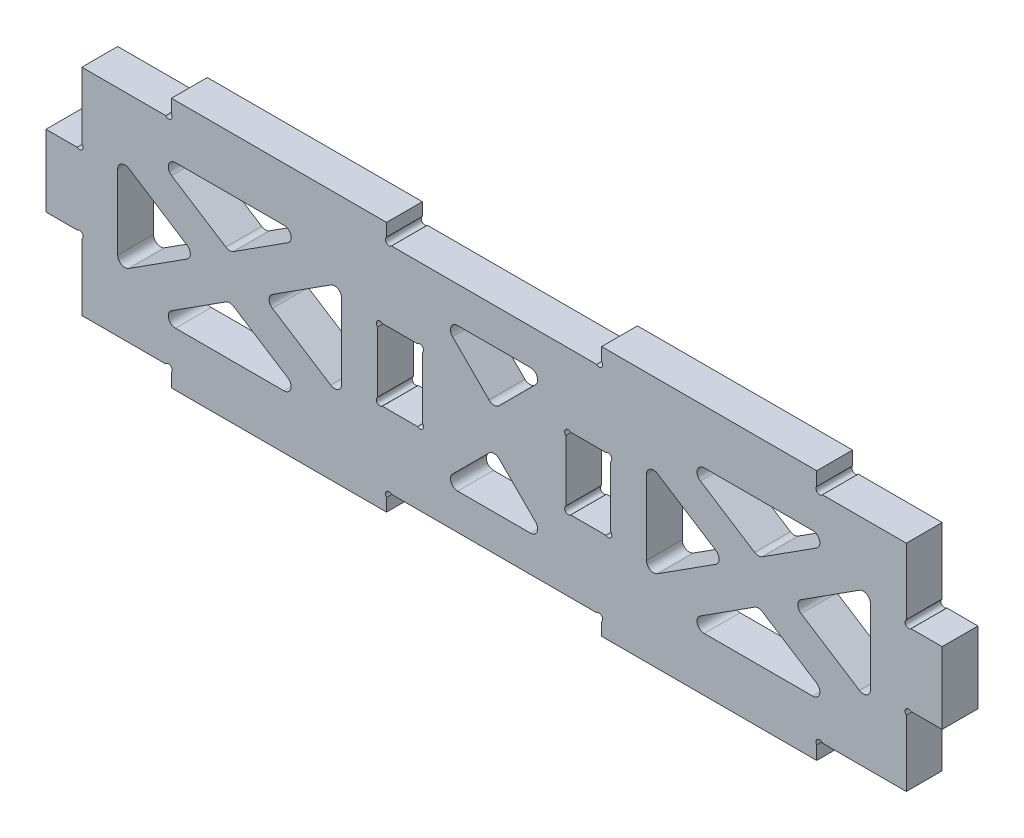
SolidWorks part; units mm, degrees
material "7050-T73510"
ref_plane "Front Plane" through (0, 0, 0) normal (0, 0, 1) x (1, 0, 0)
ref_plane "Top Plane" through (0, 0, 0) normal (0, 1, 0) x (1, 0, 0)
ref_plane "Right Plane" through (0, 0, 0) normal (1, 0, 0) x (0, 0, -1)
sketch "Sketch1" plane through (0, 0, 0) normal (0, 0, 1) x (1, 0, 0)
  line L1 (-158.75, -38.1) -> (158.75, -38.1)
  line L2 (-158.75, -38.1) -> (-158.75, 38.1)
  line L3 (-158.75, 38.1) -> (158.75, 38.1)
  line L4 (158.75, -38.1) -> (158.75, 38.1)
  line L5 (-158.75, -38.1) -> (158.75, 38.1) construction
  line L6 (-158.75, 38.1) -> (158.75, -38.1) construction
  point P0 (0, 0)
  dimension "D1" = 317.5
  dimension "D2" = 76.2
extrude "Boss-Extrude1" add sketch "Sketch1" along normal blind 12.7 contours L1 L3 region at (0, 0, 0)
sketch "Sketch2" plane through (0, 0, 12.7) normal (0, 0, 1) x (1, 0, 0)
  line L0 (-158.75, -38.1) -> (158.75, -38.1) construction
  line L1 (-38.1, -38.1) -> (-114.3, -38.1)
  line L2 (-38.1, -38.1) -> (-38.1, -44.45)
  line L3 (-38.1, -44.45) -> (-114.3, -44.45)
  line L4 (-114.3, -38.1) -> (-114.3, -44.45)
  line L5 (0, -55) -> (0, 55) construction
  line L6 (38.1, -44.45) -> (114.3, -44.45)
  line L7 (114.3, -38.1) -> (114.3, -44.45)
  line L8 (38.1, -38.1) -> (114.3, -38.1)
  line L9 (38.1, -38.1) -> (38.1, -44.45)
  line L10 (55, 0) -> (-55, 0) construction
  line L11 (38.1, 38.1) -> (38.1, 44.45)
  line L12 (38.1, 38.1) -> (114.3, 38.1)
  line L13 (114.3, 38.1) -> (114.3, 44.45)
  line L14 (38.1, 44.45) -> (114.3, 44.45)
  line L15 (-38.1, 44.45) -> (-114.3, 44.45)
  line L16 (-114.3, 38.1) -> (-114.3, 44.45)
  line L17 (-38.1, 38.1) -> (-114.3, 38.1)
  line L18 (-38.1, 38.1) -> (-38.1, 44.45)
  point P12 (-38.1, -41.275)
  dimension "D1" = 76.2
  dimension "D2" = 6.35
  dimension "D3" = 76.2
extrude "Boss-Extrude2" add sketch "Sketch2" against normal blind 12.7
sketch "Sketch3" plane through (0, 0, 12.7) normal (0, 0, 1) x (1, 0, 0)
  line L0 (55, 0) -> (-55, 0) construction
  line L1 (-158.75, -38.1) -> (-146.05, -38.1)
  line L2 (-158.75, -38.1) -> (-158.75, -12.7)
  line L3 (-158.75, -12.7) -> (-146.05, -12.7)
  line L4 (-146.05, -38.1) -> (-146.05, -12.7)
  line L6 (-158.75, 12.7) -> (-146.05, 12.7)
  line L7 (-146.05, 38.1) -> (-146.05, 12.7)
  line L8 (-158.75, 38.1) -> (-146.05, 38.1)
  line L9 (-158.75, 38.1) -> (-158.75, 12.7)
  line L10 (0, -55) -> (0, 55) construction
  line L11 (158.75, 38.1) -> (158.75, 12.7)
  line L12 (158.75, 38.1) -> (146.05, 38.1)
  line L13 (146.05, 38.1) -> (146.05, 12.7)
  line L14 (158.75, 12.7) -> (146.05, 12.7)
  line L15 (158.75, -12.7) -> (146.05, -12.7)
  line L16 (146.05, -38.1) -> (146.05, -12.7)
  line L17 (158.75, -38.1) -> (146.05, -38.1)
  line L18 (158.75, -38.1) -> (158.75, -12.7)
  line L19 (25.4, 12.7) -> (41.275, 12.7)
  line L20 (25.4, 12.7) -> (25.4, -12.7)
  line L21 (25.4, -12.7) -> (41.275, -12.7)
  line L22 (41.275, 12.7) -> (41.275, -12.7)
  line L23 (-38.1, -38.1) -> (38.1, -38.1) construction
  line L24 (-25.4, -12.7) -> (-41.275, -12.7)
  line L25 (-41.275, 12.7) -> (-41.275, -12.7)
  line L26 (-25.4, 12.7) -> (-41.275, 12.7)
  line L27 (-25.4, 12.7) -> (-25.4, -12.7)
  line L28 (-38.1, 38.1) -> (38.1, 38.1) construction
  dimension "D1" = 25.4
  dimension "D2" = 12.7
  dimension "D3" = 50.8
  dimension "D4" = 15.875
  dimension "D5" = 25.4
  dimension "D6" = 25.4
extrude "Cut-Extrude1" cut sketch "Sketch3" against normal through all
sketch "Sketch4" plane through (0, 0, 12.7) normal (0, 0, 1) x (1, 0, 0)
  line L0 (6.985, 0) -> (-6.985, 0) construction
  line L1 (-133.35, -25.4) -> (-53.975, -25.4)
  line L2 (-133.35, -25.4) -> (-133.35, 25.4)
  line L3 (-133.35, 25.4) -> (-53.975, 25.4)
  line L4 (-53.975, -25.4) -> (-53.975, 25.4)
  line L5 (-133.35, 25.4) -> (-133.4571, 24.9525)
  line L6 (-19.05, 25.4) -> (0, 6.35)
  line L7 (-146.05, 12.7) -> (-146.05, 38.1) construction
  line L8 (-41.275, 12.7) -> (-41.275, -12.7) construction
  line L9 (-146.05, 38.1) -> (-114.3, 38.1) construction
  line L10 (-133.35, 25.4) -> (-53.975, -25.4) construction
  line L11 (-133.35, -25.4) -> (-53.975, 25.4) construction
  line L12 (-133.35, 17.8609) -> (-105.4424, 0)
  line L13 (-121.5701, -25.4) -> (-93.6625, -7.5391)
  line L14 (-121.5701, 25.4) -> (-93.6625, 7.5391)
  line L15 (-133.35, -17.8609) -> (-105.4424, 0)
  line L16 (0, -6.985) -> (0, 6.985) construction
  line L17 (0, 6.35) -> (19.05, 25.4)
  line L18 (-129.927, -30.7484) -> (-50.552, 20.0516) construction
  line L19 (0, -6.35) -> (19.05, -25.4)
  line L20 (-136.773, -20.0516) -> (-57.398, 30.7484) construction
  line L21 (-136.773, 20.0516) -> (-57.398, -30.7484) construction
  line L22 (-129.927, 30.7484) -> (-50.552, -20.0516) construction
  line L23 (-81.8826, 0) -> (-53.975, 17.8609)
  line L24 (-93.6625, -7.5391) -> (-65.7549, -25.4)
  line L25 (-19.05, -25.4) -> (0, -6.35)
  line L26 (-38.1, -38.1) -> (38.1, -38.1) construction
  line L42 (-19.05, -25.4) -> (19.05, -25.4)
  line L43 (-146.05, -38.1) -> (-114.3, -38.1) construction
  line L44 (-19.05, -25.4) -> (-19.05, 25.4)
  line L45 (-19.05, 25.4) -> (19.05, 25.4)
  line L46 (19.05, -25.4) -> (19.05, 25.4)
  line L56 (-93.6625, 7.5391) -> (-65.7549, 25.4)
  line L57 (-81.8826, 0) -> (-53.975, -17.8609)
  point P0 (-93.6625, 0)
  point P54 (0, 0)
  dimension "D1" = 12.7
  dimension "D2" = 12.7
  dimension "D3" = 12.7
  dimension "D7" = 12.7
  dimension "D10" = 12.7
  dimension "D9" = 12.7
  dimension "D8" = 38.1
  dimension "D4" = 6.35
  dimension "D5" = 6.35
sketch "Sketch7" plane through (0, 0, 12.7) normal (0, 0, 1) x (1, 0, 0)
  line L0 (0, -6.985) -> (0, 6.985) construction
  line L1 (6.985, 0) -> (-6.985, 0) construction
  circle A1 centre (-115.3222, -38.8536) radius 1.27
  circle A2 centre (-37.2199, -39.0156) radius 1.27
  circle A3 centre (37.2199, -39.0156) radius 1.27
  circle A4 centre (115.3222, -38.8536) radius 1.27
  circle A7 centre (115.3222, 38.8536) radius 1.27
  circle A8 centre (37.2199, 39.0156) radius 1.27
  circle A9 centre (-37.2199, 39.0156) radius 1.27
  circle A10 centre (-115.3222, 38.8536) radius 1.27
  circle A12 centre (-146.8896, -13.6529) radius 1.27
  circle A15 centre (-146.8896, 13.6529) radius 1.27
  circle A16 centre (146.8896, -13.6529) radius 1.27
  circle A17 centre (146.8896, 13.6529) radius 1.27
  point P29 (146.8896, 13.6529)
  dimension "D1" = 2.54
  dimension "D2" = 2.54
extrude "Cut-Extrude4" cut sketch "Sketch7" against normal through all
sketch "Sketch8" plane through (0, 0, 12.7) normal (0, 0, 1) x (1, 0, 0)
  line L0 (6.985, 0) -> (-6.985, 0) construction
  line L1 (0, -6.985) -> (0, 6.985) construction
  circle A0 centre (-40.4413, 11.7419) radius 1.27
  circle A1 centre (-26.2661, 11.7711) radius 1.27
  circle A2 centre (-26.2661, -11.7711) radius 1.27
  circle A3 centre (-40.4413, -11.7419) radius 1.27
  circle A4 centre (40.4413, -11.7419) radius 1.27
  circle A5 centre (26.2661, -11.7711) radius 1.27
  circle A6 centre (26.2661, 11.7711) radius 1.27
  circle A7 centre (40.4413, 11.7419) radius 1.27
extrude "Cut-Extrude5" cut sketch "Sketch8" against normal through all
extrude "Cut-Extrude6" cut sketch "Sketch4" against normal through all contours L24 L13 L1 | L2 L15 L12 | L14 L56 L3 | L23 L57 L4 | L25 L42 L19 | L45 L6 L17 region at (-93.6625, -19.4464, 12.7) region at (-124.0475, 0, 12.7) region at (-63.2775, 0, 12.7) region at (-93.6625, 19.4464, 12.7) region at (0, 19.05, 12.7) region at (0, -19.05, 12.7)
mirror "Mirror1" about plane through (0, 0, 0) normal (1, 0, 0) of "Cut-Extrude6"
fillet "Fillet1" radius 2.54 30 edges at (-19.05, -25.4, 6.35) (-19.05, 25.4, 6.35) (-133.35, 17.8609, 6.35) (-65.7549, -25.4, 6.35) (-121.5701, -25.4, 6.35) (-133.35, -17.8609, 6.35) (-53.975, -17.8609, 6.35) (-53.975, 17.8609, 6.35) (-105.4424, 0, 6.35) (-65.7549, 25.4, 6.35) (-93.6625, 7.5391, 6.35) (-93.6625, -7.5391, 6.35) (-81.8826, 0, 6.35) (-121.5701, 25.4, 6.35) (65.7549, 25.4, 6.35) (121.5701, 25.4, 6.35) (133.35, 17.8609, 6.35) (105.4424, 0, 6.35) (65.7549, -25.4, 6.35) (121.5701, -25.4, 6.35) (93.6625, -7.5391, 6.35) (81.8826, 0, 6.35) (53.975, 17.8609, 6.35) (53.975, -17.8609, 6.35) (93.6625, 7.5391, 6.35) (133.35, -17.8609, 6.35) (19.05, -25.4, 6.35) (0, -6.35, 6.35) (19.05, 25.4, 6.35) (0, 6.35, 6.35)
